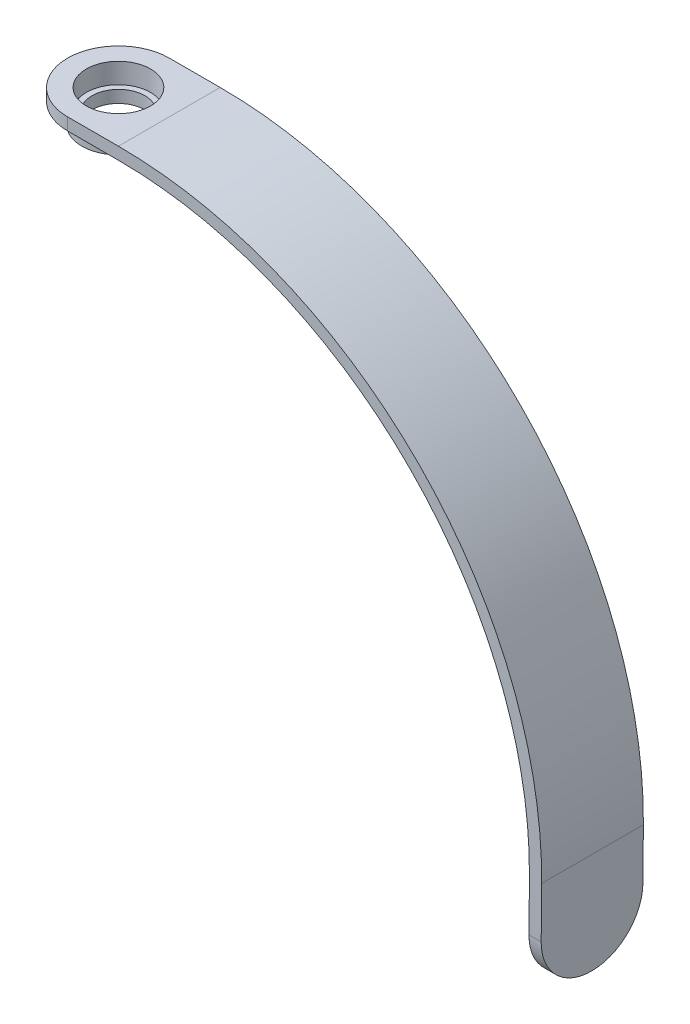
SolidWorks part; units mm, degrees
ref_plane "Front Plane" through (0, 0, 0) normal (0, 0, 1) x (1, 0, 0)
ref_plane "Top Plane" through (0, 0, 0) normal (0, 1, 0) x (1, 0, 0)
ref_plane "Right Plane" through (0, 0, 0) normal (1, 0, 0) x (0, 0, -1)
sketch "Sketch2" plane through (0, 0, 0) normal (0, 0, 1) x (1, 0, 0)
  line L0 (0, 0) -> (0, 101) construction
  line L1 (0, 0) -> (100.9962, -0.8814) construction
  line L4 (0, 104) -> (-25, 104)
  line L5 (-25, 104) -> (-25, 101)
  line L6 (-25, 101) -> (0, 101)
  line L7 (100.9962, -0.8814) -> (100.778, -25.8804)
  line L8 (100.778, -25.8804) -> (103.7779, -25.9066)
  line L9 (103.7779, -25.9066) -> (103.996, -0.9076)
  arc A0 (0, 101) -> (100.9962, -0.8814) centre (0, 0) cw
  arc A1 (0, 104) -> (103.996, -0.9076) centre (0, 0) cw
  dimension "D2" = 101
  dimension "D1" = 90.5
  dimension "D3" = 3
  dimension "D4" = 25
  dimension "D5" = 25
extrude "Boss-Extrude1" add sketch "Sketch2" along normal blind 25
fillet "Fillet1" radius 12.5 4 edges at (102.2779, -25.8935, 0) (102.2779, -25.8935, 25) (-25, 102.5, 25) (-25, 102.5, 0)
sketch "Sketch4" plane through (100.9962, -0.8814, 0) normal (-1, 0.0087, 0) x (0, 0, 1)
  circle A0 centre (12.5, -12.5) radius 3.225
  dimension "D1" = 6.45
extrude "Boss-Extrude2" add sketch "Sketch4" along normal blind 6
sketch "Sketch5" plane through (0, 104, 0) normal (0, -1, 0) x (1, 0, 0)
  circle A0 centre (-12.5, 12.5) radius 7.89
  dimension "D1" = 15.78
sketch "Sketch6" plane through (0, 101, 0) normal (0, 1, 0) x (1, 0, 0)
  circle A0 centre (-12.5, -12.5) radius 9
  circle A1 centre (-12.5, -12.5) radius 6.5
  dimension "D1" = 18
  dimension "D2" = 13
extrude "Boss-Extrude3" add sketch "Sketch6" against normal blind 5
extrude "Cut-Extrude1" cut sketch "Sketch5" along normal blind 5
equation "\"D1@Sketch2\"=362/4"
